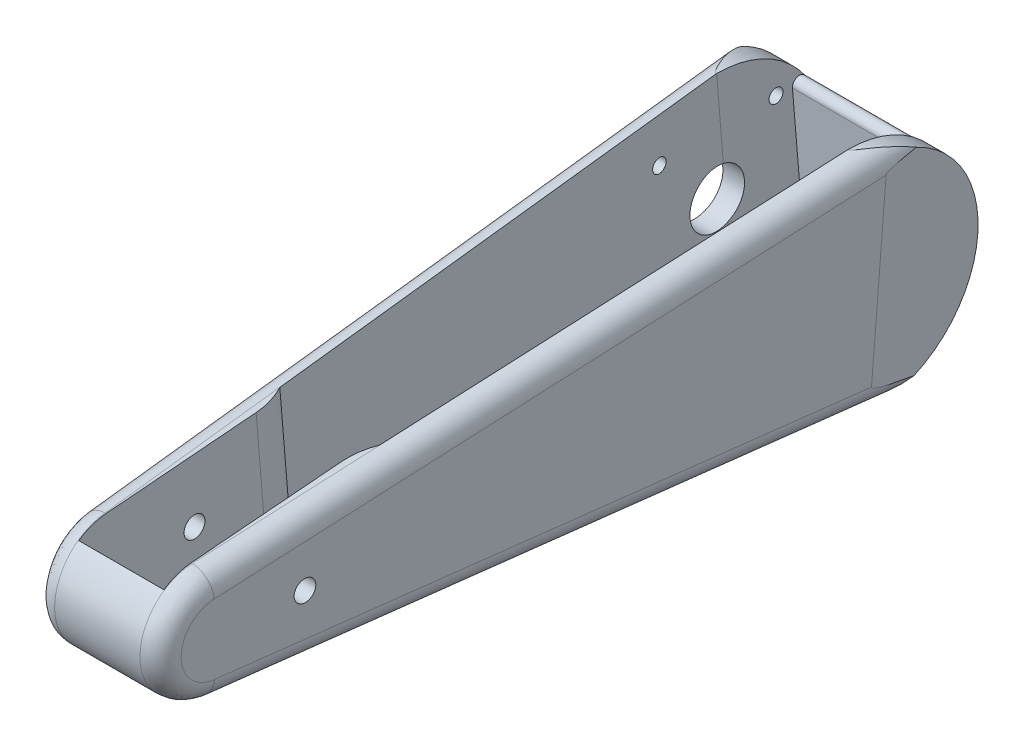
SolidWorks part; units mm, degrees
material "PLA"
ref_plane "Front Plane" through (0, 0, 0) normal (1, 0, 0) x (0, 1, 0)
ref_plane "Top Plane" through (0, 0, 0) normal (0, 0, 1) x (0, 1, 0)
ref_plane "Right Plane" through (0, 0, 0) normal (0, 1, 0) x (-1, 0, 0)
sketch "Sketch1" plane through (0, 0, 0) normal (1, 0, 0) x (0, 0, -1)
  line L0 (0, 15.5) -> (-90.6619, 7.9726)
  line L1 (0, 0) -> (0, 22.3448) construction
  line L2 (-90.6619, -7.9726) -> (0, -15.5)
  circle A0 centre (0, 0) radius 15.5
  arc A1 (-90.6619, 7.9726) -> (-90.6619, -7.9726) centre (-90, 0) ccw
  dimension "D1" = 31
  dimension "D3" = 8
  dimension "D2" = 90
extrude "Boss-Extrude1" add sketch "Sketch1" along normal blind 25 contours L0 A0 L2 | L0 L2 A0 | L0 A1 L2 region at (0, 0, -0.0003) region at (0, 0, 50.0356)
sketch "Sketch4" plane through (0, -15.3939, 1.2781) normal (0, -0.9966, 0.0827) x (1, 0, 0)
  line L0 (0, -1.2825) -> (3.5, 97.6914)
  line L1 (25, 97.6914) -> (0, 97.6914) construction
  line L2 (3.5, 97.6914) -> (21.5, 97.6914)
  line L3 (21.5, 97.6914) -> (25, -1.2825)
  line L4 (25, -1.2825) -> (0, -1.2825)
  line L5 (3.5, 97.6914) -> (0, 97.6914)
  line L6 (25, -1.2825) -> (25, 97.6914)
  line L7 (0, 97.6914) -> (0, -1.2825)
  line L8 (25, 97.6914) -> (21.5, 97.6914)
  line M6 (0, 89.6914) -> (0, -1.2825)
  line M8 (25, -1.2825) -> (25, 89.6914)
  line M9 (25, 89.6914) -> (0, 89.6914)
  dimension "D1" = 18
extrude "Cut-Extrude1" cut sketch "Sketch4" against normal up to next contours L0 M6 M9 | L5 L7 L0 M9 | L6 L8 L3 M9 | L3 M9 M8 region at (1.0724, -10.4817, 60.4413) region at (1.6803, -7.6369, 94.7042) region at (23.9276, -10.4817, 60.4413) region at (23.3197, -7.6369, 94.7042)
sketch "Sketch7" plane through (0, 15.3939, 1.2781) normal (0, 0.9966, 0.0827) x (-1, 0, 0)
  line L0 (-0.0907, -1.2825) -> (-24.9093, -1.2825)
  line L1 (-21.7362, 89.6914) -> (-3.2638, 89.6914)
  line L2 (-18.7344, 89.6914) -> (-21.9075, -1.2825)
  line L3 (-6.2656, 89.6914) -> (-3.0925, -1.2825)
  line L4 (-24.9093, -1.2825) -> (-21.7362, 89.6914) construction
  line L5 (-3.2638, 89.6914) -> (-0.0907, -1.2825) construction
  line L6 (-21.9075, -1.2825) -> (-21.9075, -11.5)
  line L7 (-21.9075, -11.5) -> (-3.0925, -11.5)
  line L8 (-3.0925, -11.5) -> (-3.0925, -1.2825)
  line L9 (-25, -15.5) -> (0, -15.5) construction
  line L10 (-18.7344, 89.6914) -> (-18.5949, 93.6914)
  line L11 (-18.5949, 93.6914) -> (-6.4051, 93.6914)
  line L12 (-6.4051, 93.6914) -> (-6.2656, 89.6914)
  line L13 (-3.4961, 97.6914) -> (-21.5039, 97.6914) construction
  line L14 (-18.5949, 93.6914) -> (-18.5949, 63.6914)
  line L15 (-18.5949, 63.6914) -> (-6.4051, 63.6914)
  line L16 (-6.4051, 63.6914) -> (-6.4051, 93.6914)
  line L17 (-6.4051, 63.6914) -> (-5.3587, 63.6914)
  line L18 (-18.5949, 63.6914) -> (-19.6413, 63.6914)
  line M11 (-3.2638, 89.6914) -> (-21.7362, 89.6914)
  dimension "D1" = 3
  dimension "D2" = 3
  dimension "D3" = 4
  dimension "D4" = 4
  dimension "D5" = 30
extrude "Cut-Extrude2" cut sketch "Sketch7" against normal up to next contours L3 L1 L2 L0 | L7 L8 L0 L6 | L15 L16 L14 M11 | L16 L11 L14 M11 region at (12.5, 15.9227, -5.0912) region at (12.5, 12.9346, 30.8977) region at (12.5, 9.0482, 77.7065) region at (12.5, 7.8071, 92.6551)
fillet "Fillet1" radius 10 2 edges at (6.4051, -0.0703, 63.9047) (18.5949, -0.0703, 63.9047)
fillet "Fillet2" radius 3 6 edges at (23.3915, -11.7363, 45.331) (21.501, 0, 98) (1.6085, -11.7363, 45.331) (3.499, 0, 98) (23.3228, 11.7363, 45.331) (1.6772, 11.7363, 45.331)
fillet "Fillet3" radius 1 2 edges at (12.5, -9.4051, -12.3205) (12.5, 11.3082, -10.6007)
sketch "Sketch9" plane through (0, 0, 0) normal (1, 0, 0) x (0, 1, 0)
  line L0 (0, 98) -> (0, 78) construction
  line L1 (0, 0) -> (0, 82.8492) construction
  circle A0 centre (0, 78) radius 1.5
  arc A1 (7.9726, 90.6619) -> (-7.9726, 90.6619) centre (0, 90) ccw construction
  dimension "D1" = 3
  dimension "D2" = 20
extrude "Cut-Extrude4" cut sketch "Sketch9" along normal through all both and the other way through all
sketch "Sketch12" plane through (0, 0, 0) normal (1, 0, 0) x (0, 1, 0)
  line L1 (-8.5, -8.5) -> (8.5, -8.5)
  line L2 (-8.5, -8.5) -> (-8.5, 8.5)
  line L3 (-8.5, 8.5) -> (8.5, 8.5)
  line L4 (8.5, -8.5) -> (8.5, 8.5)
  line L5 (0, 8.5) -> (0, -8.5) construction
  line L6 (-8.5, 0) -> (8.5, 0) construction
  circle A0 centre (-8.5, 8.5) radius 1
  circle A1 centre (8.5, 8.5) radius 1
  circle A2 centre (8.5, -8.5) radius 1
  circle A3 centre (-8.5, -8.5) radius 1
  point P0 (0, 0)
  dimension "D1" = 2
  dimension "D2" = 17
extrude "Cut-Extrude5" cut sketch "Sketch12" along normal up to next and the other way through all contours L3 A1 L4 | L4 A1 L3 | L1 A2 L4 | L4 A2 L1 | L2 A0 L3 | L3 A0 L2 | L2 A3 L1 | L1 A3 L2 region at (0, -8.0756, -8.0756) region at (0, -8.6415, -8.6415) region at (0, 8.0756, -8.0756) region at (0, 8.6415, -8.6415) region at (0, -8.6415, 8.6415) region at (0, -8.0756, 8.0756) region at (0, 8.0756, 8.0756) region at (0, 8.6415, 8.6415)
sketch "Sketch13" plane through (0, 0, 0) normal (1, 0, 0) x (0, 1, 0)
  circle A0 centre (0, 0) radius 4
  dimension "D1" = 8
extrude "Cut-Extrude6" cut sketch "Sketch13" along normal up to next
